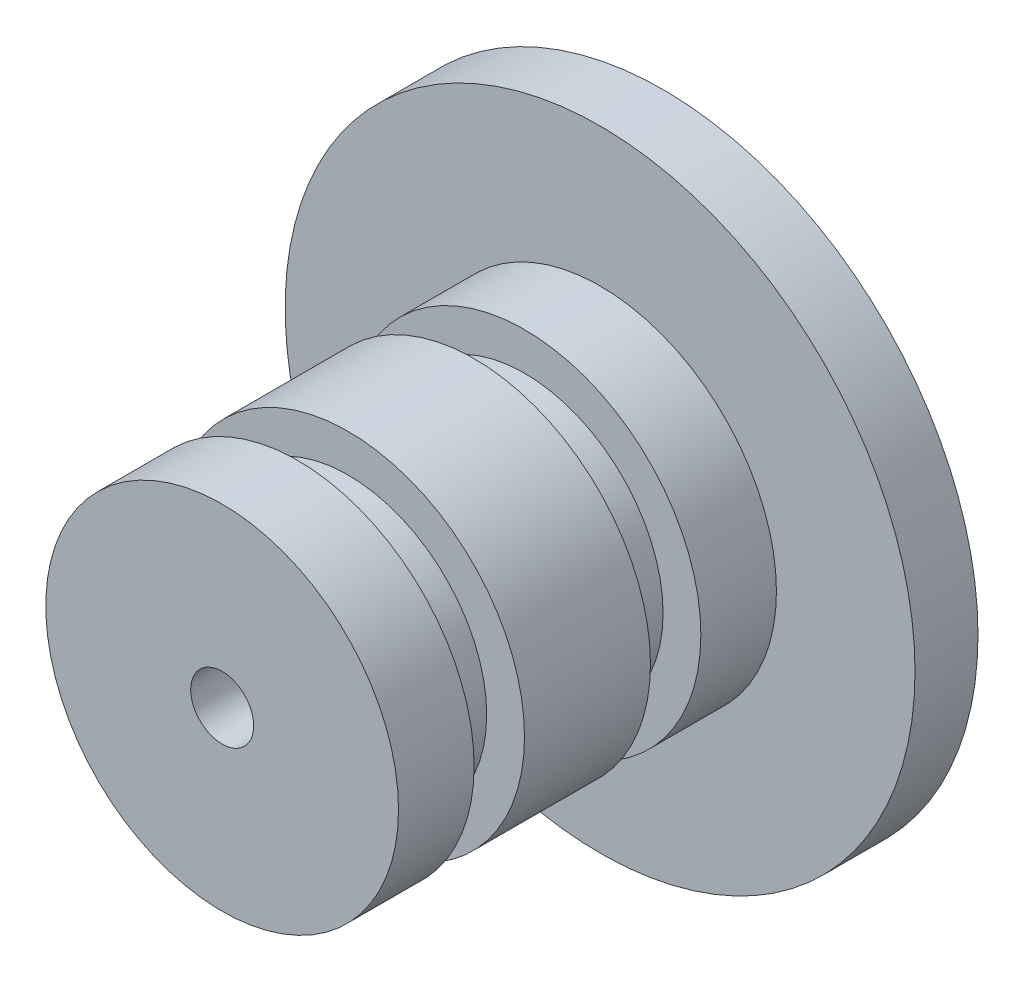
SolidWorks part; units mm, degrees
ref_plane "Front Plane" through (0, 0, 0) normal (0, 0, 1) x (1, 0, 0)
ref_plane "Top Plane" through (0, 0, 0) normal (0, 1, 0) x (1, 0, 0)
ref_plane "Right Plane" through (0, 0, 0) normal (1, 0, 0) x (0, 0, -1)
sketch "Sketch2" plane through (0, 0, 0) normal (0, 1, 0) x (1, 0, 0)
  line L0 (0, 0) -> (-25, 0)
  line L1 (-25, 0) -> (-25, -5)
  line L2 (-25, -5) -> (-14, -5)
  line L3 (-14, -5) -> (-14, -11)
  line L4 (-14, -11) -> (-11, -11)
  line L5 (-11, -11) -> (-11, -15)
  line L6 (-11, -15) -> (-14, -15)
  line L7 (-14, -15) -> (-14, -25)
  line L8 (-14, -25) -> (-11, -25)
  line L9 (-11, -25) -> (-11, -29)
  line L10 (-11, -29) -> (-14, -29)
  line L11 (-14, -29) -> (-14, -35)
  line L12 (-14, -35) -> (0, -35)
  line L13 (0, -35) -> (0, 0)
  dimension "D1" = 35
  dimension "D2" = 14
  dimension "D3" = 4
  dimension "D4" = 3
  dimension "D5" = 5
  dimension "D6" = 6
  dimension "D7" = 10
  dimension "D8" = 25
revolve "Revolve1" add sketch "Sketch2" angle 360 about L13
sketch "Sketch4" plane through (0, 0, 0) normal (0, 0, -1) x (-1, 0, 0)
  circle A0 centre (0, 0) radius 2.5
  dimension "D1" = 5
extrude "Cut-Extrude1" cut sketch "Sketch4" against normal through all
thread "Thread1" pitch 1 method cut profile "Thread Profile1" start angle 0, offset 0, length 12, pitch 1, diameter 5
ref_plane "Plane1" through (2.5, 0, 0) normal (0, -1, 0) x (1, 0, 0)
sketch "Thread Profile1" plane through (2.5, 0, 0) normal (0, -1, 0) x (1, 0, 0)
  line L0 (0, 0) -> (0, 1) construction
  line L1 (0, 0) -> (0.5413, 0.3125)
  line L2 (0.5413, 0.3125) -> (0.5413, 0.4375)
  line L3 (0.5413, 0.4375) -> (0, 0.75)
  line L4 (0.5413, 0.375) -> (0, 0.375) construction
  line L11 (0, 0) -> (0, 0.75)
  point P2 (0, 0)
  dimension "Pitch" = 1
  dimension "Profile_Angle" = 60
  dimension "Profile_Land" = 0.125
  dimension "Profile_Height" = 0.5413
